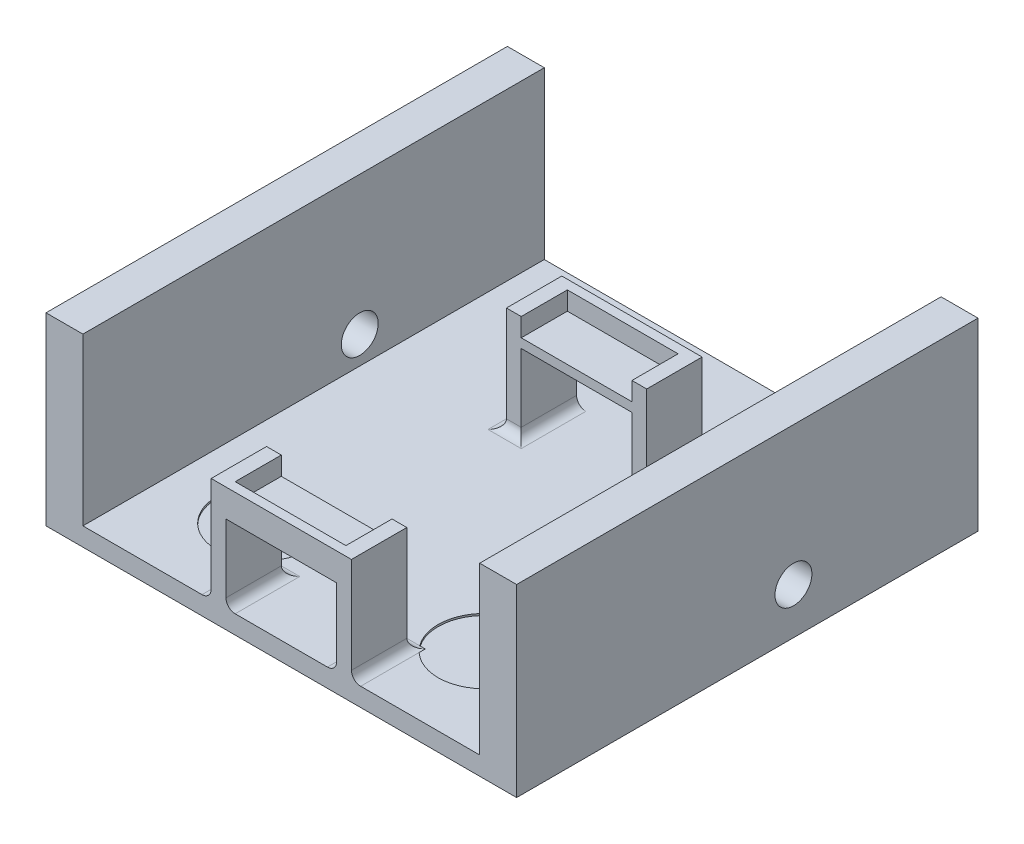
SolidWorks part; units mm, degrees
ref_plane "前基準面" through (0, 0, 0) normal (0, 0, 1) x (1, 0, 0)
ref_plane "上基準面" through (0, 0, 0) normal (0, 1, 0) x (1, 0, 0)
ref_plane "右基準面" through (0, 0, 0) normal (1, 0, 0) x (0, 0, -1)
sketch "草圖4" plane through (0, 0, 0) normal (0, 1, 0) x (1, 0, 0)
  line L1 (-127.5, 125) -> (127.5, 125)
  line L2 (-127.5, 125) -> (-127.5, -125)
  line L3 (-127.5, -125) -> (127.5, -125)
  line L4 (127.5, 125) -> (127.5, -125)
  line L5 (-127.5, 125) -> (127.5, -125) construction
  line L6 (-127.5, -125) -> (127.5, 125) construction
  point P0 (0, 0)
  dimension "D1" = 255
  dimension "D2" = 250
extrude "填料-伸長2" add sketch "草圖4" along normal blind 10
sketch "草圖7" plane through (0, 10, 0) normal (0, 1, 0) x (1, 0, 0)
  line L0 (-127.5, -125) -> (127.5, -125) construction
  line L1 (-127.5, 125) -> (-107.5, 125)
  line L2 (-127.5, 125) -> (-127.5, -125)
  line L3 (-127.5, -125) -> (-107.5, -125)
  line L4 (-107.5, 125) -> (-107.5, -125)
  line L5 (127.5, 125) -> (-127.5, 125) construction
  line L6 (127.5, -125) -> (107.5, -125)
  line L7 (127.5, -125) -> (127.5, 125)
  line L8 (127.5, 125) -> (107.5, 125)
  line L9 (107.5, -125) -> (107.5, 125)
  line L10 (0, 160.1697) -> (0, -166.2631) construction
  line L20 (42.5, -150) -> (-42.5, -150) construction
  line L21 (42.5, -150) -> (42.5, 110) construction
  line L22 (42.5, 110) -> (-42.5, 110) construction
  line L23 (-42.5, -150) -> (-42.5, 110) construction
  dimension "D1" = 20
  dimension "D2" = 20
  dimension "D4" = 260
  dimension "D5" = 85
extrude "填料-伸長3" add sketch "草圖7" along normal blind 90
sketch "草圖8" plane through (0, 0, 125) normal (0, 0, 1) x (1, 0, 0)
  line L0 (0, 114.0362) -> (0, -18.6102) construction
  line L1 (-30, 10) -> (-38, 10)
  line L2 (-107.5, 10) -> (107.5, 10) construction
  line L3 (-38, 10) -> (-38, 67)
  line L4 (-38, 67) -> (-30, 67)
  line L7 (-30, 52) -> (-30, 10)
  line L10 (38, 67) -> (30, 67)
  line L11 (38, 10) -> (38, 67)
  line L12 (30, 10) -> (38, 10)
  line L13 (30, 52) -> (30, 10)
  line L14 (30, 57) -> (30, 67)
  line L15 (-30, 57) -> (-30, 67)
  line L16 (30, 57) -> (-30, 57)
  line L17 (-30, 52) -> (30, 52)
  dimension "D1" = 60
  dimension "D2" = 8
  dimension "D3" = 60
  dimension "D4" = 10
  dimension "D5" = 57
  dimension "D6" = 30
  dimension "D7" = 5
extrude "填料-伸長4" add sketch "草圖8" against normal blind 30
sketch "草圖9" plane through (-127.5, 0, 0) normal (-1, 0, 0) x (0, 0, 1)
  line L0 (-125, 0) -> (125, 0) construction
  line L2 (-125, 100) -> (-125, 0) construction
  circle A0 centre (-25, 25) radius 10
  dimension "D1" = 20
  dimension "D2" = 25
  dimension "D3" = 100
extrude "除料-伸長1" cut sketch "草圖9" against normal up to next
mirror "鏡射1" about plane through (0, 0, 0) normal (1, 0, 0) of "除料-伸長1"
sketch "草圖11" plane through (0, 0, 125) normal (0, 0, 1) x (1, 0, 0)
  line L10 (0, 0) -> (0, 84.8358) construction
  line L11 (-127.5, 0) -> (127.5, 0) construction
  line L23 (-30, 57) -> (30, 57)
  line L24 (-30, 57) -> (-30, 67)
  line L25 (-30, 67) -> (30, 67)
  line L26 (30, 57) -> (30, 67)
extrude "填料-伸長6" add sketch "草圖11" against normal blind 5
fillet "圓角1" radius 5 6 edges at (38, 10, 110) (-38, 10, 110) (30, 10, 110) (-30, 10, 110) (-34, 10, 95) (34, 10, 95)
ref_plane "平面1" through (0, 0, 30) normal (0, 0, -1) x (-1, 0, 0)
mirror "鏡射2" about plane through (0, 0, 30) normal (0, 0, -1) of "填料-伸長6", "填料-伸長4", "圓角1"
sketch "草圖12" plane through (0, 10, 0) normal (0, 1, 0) x (1, 0, 0)
  line L0 (0, -117.67) -> (0, 45.3288) construction
  line L1 (-60, -75) -> (60, -75) construction
  line L6 (38, -125) -> (-38, -125) construction
  circle A0 centre (0, -22.2729) radius 35 construction
  circle A1 centre (-60, -75) radius 32.5 construction
  circle A2 centre (60, -75) radius 32.5 construction
  circle A3 centre (-60, -75) radius 25
  circle A4 centre (60, -75) radius 25
  point P11 (60, -75)
  point P12 (0, -8.538)
  point P13 (0, -22.2729)
  point P16 (-60, -75)
  dimension "D1" = 70
  dimension "D2" = 65
  dimension "D5" = 50
  dimension "D3" = 60
  dimension "D4" = 50
extrude "除料-伸長2" cut sketch "草圖12" against normal blind 1
